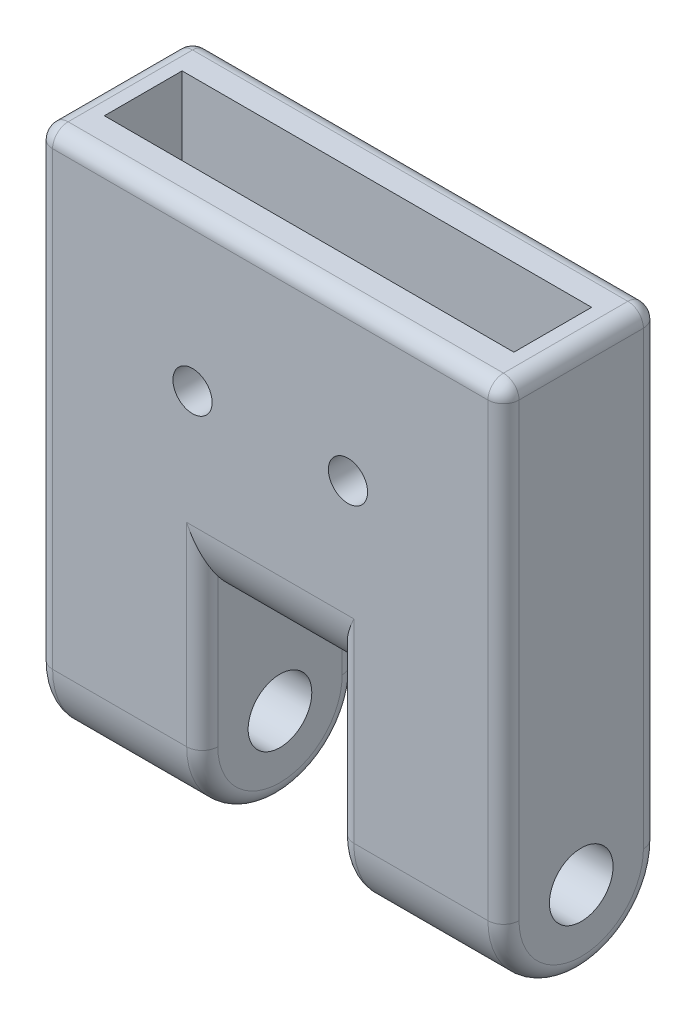
SolidWorks part; units mm, degrees
ref_plane "Front" through (0, 0, 0) normal (0, 0, 1) x (1, 0, 0)
ref_plane "Top" through (0, 0, 0) normal (0, 1, 0) x (1, 0, 0)
ref_plane "Right" through (0, 0, 0) normal (1, 0, 0) x (0, 0, -1)
sketch "Esquisse1" plane through (0, 0, 0) normal (0, 1, 0) x (1, 0, 0)
  line L1 (-19.05, 6.35) -> (19.05, 6.35)
  line L2 (-19.05, 6.35) -> (-19.05, -6.35)
  line L3 (-19.05, -6.35) -> (19.05, -6.35)
  line L4 (19.05, 6.35) -> (19.05, -6.35)
  line L5 (-19.05, 6.35) -> (19.05, -6.35) construction
  line L6 (-19.05, -6.35) -> (19.05, 6.35) construction
  point P0 (0, 0)
  dimension "D1" = 38.1
  dimension "D2" = 12.7
extrude "Boss.-Extru.1" add sketch "Esquisse1" along normal blind 3.175
sketch "Esquisse2" plane through (0, 3.175, 0) normal (0, 1, 0) x (1, 0, 0)
  line L0 (-19.05, -6.35) -> (19.05, -6.35) construction
  line L1 (-19.05, 6.35) -> (19.05, 6.35)
  line L2 (-19.05, 6.35) -> (-19.05, -6.35)
  line L3 (-19.05, -6.35) -> (19.05, -6.35)
  line L4 (19.05, 6.35) -> (19.05, -6.35)
  line L6 (-16.7259, 3.175) -> (16.7259, 3.175)
  line L7 (-16.7259, 3.175) -> (-16.7259, -3.175)
  line L8 (-16.7259, -3.175) -> (16.7259, -3.175)
  line L9 (16.7259, 3.175) -> (16.7259, -3.175)
  line L10 (-16.7259, 3.175) -> (16.7259, -3.175) construction
  line L11 (-16.7259, -3.175) -> (16.7259, 3.175) construction
  point P7 (0, 0)
  dimension "D1" = 33.4518
  dimension "D2" = 6.35
extrude "Boss.-Extru.2" add sketch "Esquisse2" along normal blind 25.4
sketch "Esquisse3" plane through (0, 0, 6.35) normal (0, 0, 1) x (1, 0, 0)
  line L0 (-6.35, 15.875) -> (6.35, 15.875) construction
  line L1 (-19.05, 28.575) -> (19.05, 28.575) construction
  circle A0 centre (-6.35, 15.875) radius 1.6
  circle A1 centre (6.35, 15.875) radius 1.6
  point P4 (0, 15.875)
  dimension "D1" = 3.2
  dimension "D2" = 3.2
  dimension "D3" = 12.7
  dimension "D4" = 12.7
extrude "Enlèv. mat.-Extru.1" cut sketch "Esquisse3" against normal blind 25.4
sketch "Esquisse4" plane through (19.05, 0, 0) normal (1, 0, 0) x (0, 0, -1)
  line L0 (-6.35, 0) -> (-6.35, -9.525)
  line L1 (6.35, -9.525) -> (6.35, 0)
  line L2 (6.35, 0) -> (-6.35, 0)
  arc A0 (-6.35, -9.525) -> (6.35, -9.525) centre (0, -9.525) ccw
  circle A1 centre (0, -9.525) radius 2.6
  dimension "D1" = 9.525
  dimension "D2" = 5.2
extrude "Boss.-Extru.3" add sketch "Esquisse4" against normal blind 13.4937
mirror "Symétrie1" about plane through (0, 0, 0) normal (1, 0, 0) of "Boss.-Extru.3"
fillet "Congé1" radius 6.35 2 edges at (0, 0, -6.35) (0, 0, 6.35)
fillet "Congé2" radius 1.27 16 edges at (19.05, 9.525, -6.35) (19.05, -15.875, 0) (19.05, 9.525, 6.35) (-5.5562, -1.5875, 6.35) (-5.5563, -1.5875, -6.35) (-19.05, 9.525, -6.35) (-19.05, -15.875, 0) (5.5563, -1.5875, -6.35) (5.5562, -15.875, 0) (19.05, 28.575, 0) (0, 28.575, -6.35) (-19.05, 28.575, 0) (0, 28.575, 6.35) (-5.5562, -15.875, 0) (-19.05, 9.525, 6.35) (5.5562, -1.5875, 6.35)
